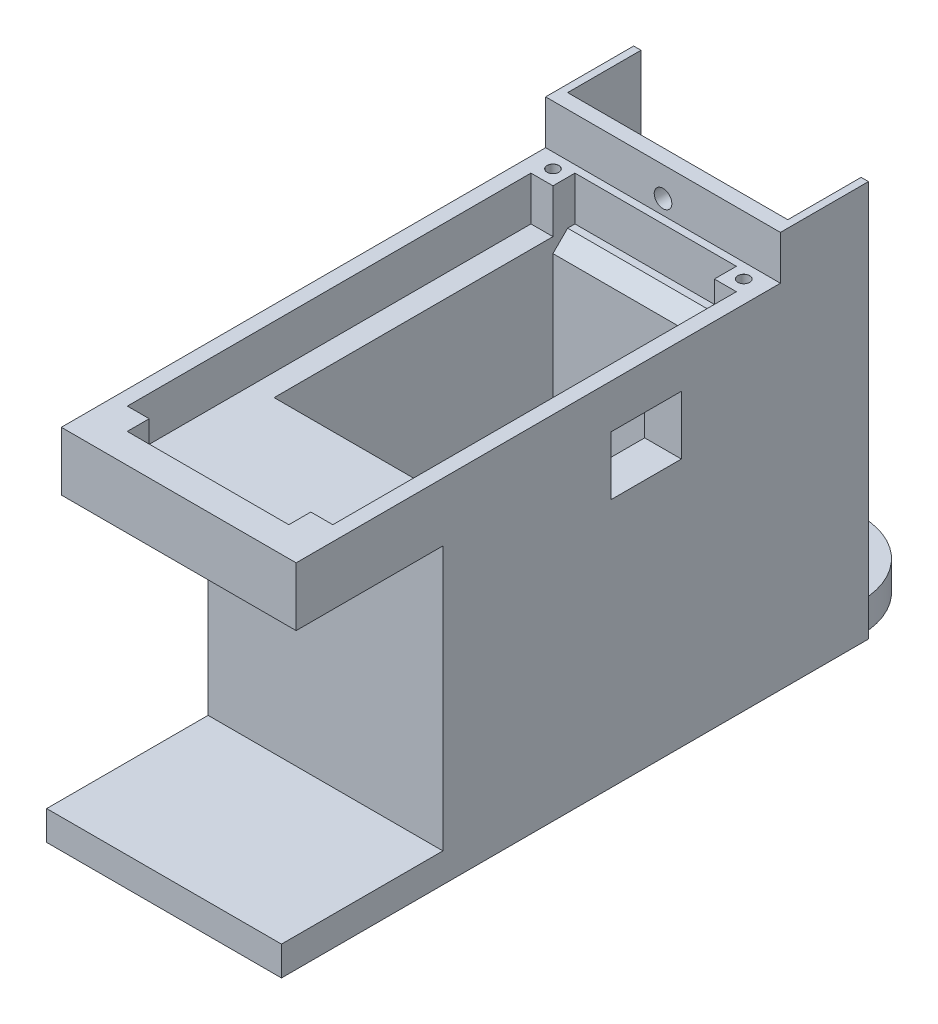
SolidWorks part; units mm, degrees
ref_plane "Front Plane" through (0, 0, 0) normal (0, 0, 1) x (1, 0, 0)
ref_plane "Top Plane" through (0, 0, 0) normal (0, 1, 0) x (1, 0, 0)
ref_plane "Right Plane" through (0, 0, 0) normal (1, 0, 0) x (0, 0, -1)
sketch "Sketch2" plane through (0, 0, 0) normal (0, 1, 0) x (1, 0, 0)
  line L0 (155, 400) -> (160, 400)
  line L1 (0, 0) -> (160, 0)
  line L2 (0, 0) -> (0, 400)
  line L3 (0, 400) -> (5, 400)
  line L4 (160, 0) -> (160, 400)
  line L6 (5, 400) -> (5, 450)
  line L7 (5, 450) -> (155, 450)
  line L8 (155, 400) -> (155, 450)
  dimension "D1" = 160
  dimension "D2" = 400
  dimension "D3" = 5
  dimension "D4" = 5
  dimension "D5" = 50
extrude "Boss-Extrude1" add sketch "Sketch2" along normal blind 20
fillet "Fillet1" radius 50 2 edges at (155, 10, -450) (5, 10, -450)
sketch "Sketch3" plane through (0, 20, 0) normal (0, 1, 0) x (1, 0, 0)
  line L0 (0, 400) -> (0, 340)
  line L1 (0, 400) -> (0, 0) construction
  line L2 (0, 340) -> (160, 340)
  line L3 (160, 0) -> (160, 400) construction
  line L4 (160, 340) -> (160, 400)
  line L5 (160, 400) -> (155, 400)
  line L6 (5, 400) -> (0, 400) construction
  line L7 (155, 400) -> (155, 350)
  line L8 (155, 350) -> (5, 350)
  line L9 (5, 350) -> (5, 400)
  line L10 (5, 400) -> (0, 400)
  dimension "D1" = 5
  dimension "D2" = 5
  dimension "D3" = 50
  dimension "D4" = 10
  dimension "D5" = 150
extrude "Boss-Extrude2" add sketch "Sketch3" along normal blind 250
sketch "Sketch4" plane through (0, 0, -340) normal (0, 0, 1) x (1, 0, 0)
  line L0 (0, 270) -> (160, 270) construction
  line L1 (0, 270) -> (0, 20) construction
  circle A0 centre (80, 250) radius 6
  dimension "D1" = 12
  dimension "D2" = 20
  dimension "D3" = 80
extrude "Cut-Extrude1" cut sketch "Sketch4" against normal blind 10
sketch "Sketch5" plane through (0, 0, -350) normal (0, 0, -1) x (-1, 0, 0)
  circle A0 centre (-80, 250) radius 6
  circle A1 centre (-80, 250) radius 8
  dimension "D1" = 16
  dimension "D2" = 12
extrude "Boss-Extrude3" add sketch "Sketch5" along normal blind 12 contours A1 | A0
fillet "Fillet2" radius 1 2 edges at (74, 250, -362) (72, 250, -362)
sketch "Sketch6" plane through (0, 20, 0) normal (0, 1, 0) x (1, 0, 0)
  line L0 (155, 350) -> (5, 350) construction
  line L1 (30, 350) -> (45, 350)
  line L2 (30, 350) -> (30, 410)
  line L3 (30, 410) -> (45, 410)
  line L4 (45, 350) -> (45, 410)
  line L5 (5, 350) -> (5, 400) construction
  line L6 (115, 350) -> (130, 350)
  line L7 (115, 350) -> (115, 410)
  line L8 (115, 410) -> (130, 410)
  line L9 (130, 350) -> (130, 410)
  line L10 (155, 400) -> (155, 350) construction
  dimension "D1" = 25
  dimension "D2" = 25
  dimension "D3" = 15
  dimension "D4" = 15
  dimension "D5" = 60
extrude "Boss-Extrude4" add sketch "Sketch6" along normal blind 6
sketch "Sketch7" plane through (0, 20, 0) normal (0, 1, 0) x (1, 0, 0)
  line L0 (0, 340) -> (0, 0) construction
  line L1 (55, 220) -> (105, 220)
  line L2 (55, 220) -> (55, 130)
  line L3 (55, 130) -> (105, 130)
  line L4 (105, 220) -> (105, 130)
  line L6 (0, 340) -> (160, 340) construction
  dimension "D1" = 50
  dimension "D2" = 55
  dimension "D3" = 90
  dimension "D4" = 120
extrude "Boss-Extrude5" add sketch "Sketch7" along normal blind 30
sketch "Sketch8" plane through (55, 0, 0) normal (-1, 0, 0) x (0, 0, 1)
  line L0 (-220, 50) -> (-130, 50) construction
  line L1 (-220, 50) -> (-220, 20) construction
  circle A0 centre (-195, 41) radius 3.3
  dimension "D1" = 6.6
  dimension "D2" = 9
  dimension "D3" = 25
extrude "Cut-Extrude2" cut sketch "Sketch8" against normal up to next
sketch "Sketch9" plane through (0, 50, 0) normal (0, 1, 0) x (1, 0, 0)
  line L0 (80, 220) -> (80, 130) construction
  line L1 (71, 186) -> (89, 186)
  line L2 (71, 186) -> (71, 204)
  line L3 (71, 204) -> (89, 204)
  line L4 (89, 186) -> (89, 204)
  line L5 (71, 186) -> (89, 204) construction
  line L6 (71, 204) -> (89, 186) construction
  line L7 (105, 220) -> (55, 220) construction
  line L8 (55, 130) -> (105, 130) construction
  line L9 (55, 175) -> (105, 175) construction
  line L10 (55, 220) -> (55, 130) construction
  line L11 (105, 130) -> (105, 220) construction
  point P0 (80, 195)
  dimension "D1" = 18
  dimension "D2" = 25
extrude "Cut-Extrude3" cut sketch "Sketch9" against normal blind 20
sketch "Sketch10" plane through (0, 50, 0) normal (0, 1, 0) x (1, 0, 0)
  line L0 (55, 130) -> (105, 130)
  line L1 (105, 130) -> (105, 220)
  line L2 (105, 220) -> (55, 220)
  line L3 (55, 220) -> (55, 130)
  line L5 (60, 214) -> (100, 214)
  line L6 (60, 214) -> (60, 159)
  line L8 (100, 214) -> (100, 159)
  arc A0 (60, 159) -> (100, 159) centre (80, 159) ccw
  dimension "D1" = 5
  dimension "D2" = 5
  dimension "D4" = 6
extrude "Boss-Extrude6" add sketch "Sketch10" along normal blind 20
chamfer "Chamfer1" distance 10 distance2 13 1 edges at (60, 60, -214) first distance on face at (60, 60, -186.5)
chamfer "Chamfer2" distance 13 distance2 10 1 edges at (100, 60, -214) first distance on face at (86.5, 60, -214)
fillet "Fillet3" radius 2 4 edges at (100, 60, -204) (87, 60, -214) (73, 60, -214) (60, 60, -204)
sketch "Sketch11" plane through (0, 20, 0) normal (0, 1, 0) x (1, 0, 0)
  line L0 (0, 340) -> (0, 110)
  line L1 (0, 110) -> (160, 110)
  line L2 (160, 110) -> (160, 340)
  line L3 (160, 340) -> (155, 340)
  line L4 (0, 340) -> (160, 340) construction
  line L5 (155, 340) -> (155, 115)
  line L6 (155, 115) -> (5, 115)
  line L7 (5, 115) -> (5, 340)
  line L8 (5, 340) -> (0, 340)
  line L9 (0, 0) -> (160, 0) construction
  dimension "D1" = 5
  dimension "D2" = 5
  dimension "D3" = 5
  dimension "D4" = 110
extrude "Boss-Extrude7" add sketch "Sketch11" along normal blind 220
sketch "Sketch12" plane through (0, 20, 0) normal (0, 1, 0) x (1, 0, 0)
  line L1 (5, 340) -> (25, 340)
  line L2 (5, 340) -> (5, 320)
  line L3 (5, 320) -> (25, 320)
  line L4 (25, 340) -> (25, 320)
  line L5 (155, 340) -> (135, 340)
  line L6 (155, 340) -> (155, 320)
  line L7 (155, 320) -> (135, 320)
  line L8 (135, 340) -> (135, 320)
  line L9 (5, 115) -> (25, 115)
  line L10 (5, 115) -> (5, 135)
  line L11 (5, 135) -> (25, 135)
  line L12 (25, 115) -> (25, 135)
  line L13 (155, 115) -> (135, 115)
  line L14 (155, 115) -> (155, 135)
  line L15 (155, 135) -> (135, 135)
  line L16 (135, 115) -> (135, 135)
  line L17 (5, 320) -> (10, 320)
  line L18 (5, 320) -> (5, 135)
  line L19 (5, 135) -> (10, 135)
  line L20 (10, 320) -> (10, 135)
  line L21 (25, 115) -> (135, 115)
  line L22 (25, 115) -> (25, 120)
  line L23 (25, 120) -> (135, 120)
  line L24 (135, 115) -> (135, 120)
  line L25 (155, 135) -> (150, 135)
  line L26 (155, 135) -> (155, 320)
  line L27 (155, 320) -> (150, 320)
  line L28 (150, 135) -> (150, 320)
  line L29 (135, 340) -> (25, 340)
  line L30 (135, 340) -> (135, 335)
  line L31 (135, 335) -> (25, 335)
  line L32 (25, 340) -> (25, 335)
  line M12 (155, 115) -> (155, 340)
  line M13 (155, 340) -> (5, 340)
  line M14 (5, 340) -> (5, 115)
  line M15 (5, 115) -> (155, 115)
  dimension "D1" = 20
  dimension "D2" = 20
  dimension "D3" = 20
  dimension "D4" = 20
  dimension "D5" = 20
  dimension "D6" = 20
  dimension "D7" = 20
  dimension "D8" = 20
  dimension "D9" = 5
  dimension "D10" = 5
  dimension "D11" = 5
  dimension "D12" = 5
extrude "Boss-Extrude8" add sketch "Sketch12" along normal blind 220 contours L23 L12 L16 M15 | L12 L11 M15 M14 | L20 L3 L11 M14 | L4 L3 M13 M14 | L31 L8 L4 M13 | L8 L7 M13 M12 | L28 L15 L7 M12 | L16 L15 M15 M12 region at (15, 20, -330) region at (80, 20, -337.5) region at (7.5, 20, -227.5) region at (145, 20, -330) region at (15, 20, -125) region at (152.5, 20, -227.5) region at (80, 20, -117.5) region at (145, 20, -125)
sketch "Sketch14" plane through (0, 240, 0) normal (0, 1, 0) x (1, 0, 0)
  line L2 (80, 340) -> (80, 115) construction
  line L3 (0, 340) -> (160, 340) construction
  line L10 (5, 227.5) -> (155, 227.5) construction
  point P0 (15, 330)
  point P31 (145, 330)
hole_wizard "Ø8.0mm Dowel Hole1" positions "Sketch14" profile "Sketch15" hole size "Ø8.0" standard "ANSI Metric"
sketch "Sketch15" plane through (15, 240, -330) normal (1, 0, 0) x (0, 0, 1)
  line L0 (0, 0) -> (0, 18.4034)
  line L1 (0, 18.4034) -> (4, 16)
  line L2 (4, 16) -> (4, 0.025)
  line L3 (4, 0.025) -> (4.025, 0)
  line L5 (4.025, 0) -> (0, 0)
  line L6 (-4, 0.025) -> (-4.025, 0) construction
  line L10 (0, 18.4034) -> (-4, 16) construction
  line L11 (0, -6.35) -> (0, 107.95) construction
  dimension "Hole Dia." = 8
  dimension "Hole Depth" = 16
  dimension "Near C'Sink Dia." = 8.05
  dimension "Near C'Sink Angle" = 90
  dimension "Drill Angle" = 118
sketch "Sketch16" plane through (0, 20, 0) normal (0, 1, 0) x (1, 0, 0)
  line L0 (25, 335) -> (135, 335)
  line L1 (135, 335) -> (25, 335) construction
  line L2 (135, 335) -> (135, 320)
  line L3 (135, 320) -> (150, 320)
  line L4 (150, 320) -> (150, 135)
  line L5 (150, 135) -> (135, 135)
  line L6 (135, 135) -> (135, 120)
  line L7 (135, 120) -> (25, 120)
  line L8 (25, 120) -> (25, 135)
  line L9 (25, 135) -> (10, 135)
  line L10 (10, 135) -> (10, 320)
  line L11 (10, 320) -> (25, 320) construction
  line L12 (10, 320) -> (10, 135) construction
  line L13 (10, 320) -> (25, 320)
  line L15 (25, 320) -> (25, 335)
  line L16 (25, 320) -> (135, 320)
  line L17 (135, 320) -> (135, 130)
  line L18 (135, 130) -> (25, 130)
  line L19 (25, 130) -> (25, 320)
  line M17 (135, 335) -> (25, 335)
  line M18 (25, 335) -> (25, 320)
  line M19 (25, 320) -> (10, 320)
  line M20 (10, 320) -> (10, 135)
  line M21 (10, 135) -> (25, 135)
  line M23 (25, 120) -> (135, 120)
  line M24 (135, 120) -> (135, 135)
  line M25 (135, 135) -> (150, 135)
  line M26 (150, 135) -> (150, 320)
  line M27 (150, 320) -> (135, 320)
  line M28 (135, 320) -> (135, 335)
  line M32 (105, 130) -> (55, 130)
  dimension "D1" = 15
  dimension "D2" = 15
  dimension "D3" = 10
extrude "Boss-Extrude9" add sketch "Sketch16" along normal blind 190 contours L19 M21 M19 M20 | L16 M18 M28 M17 | L17 M27 M25 M26 | L18 L8 M24 M32 M23 region at (80, 20, -327.5) region at (17.5, 20, -227.5) region at (142.5, 20, -227.5) region at (80, 20, -125)
chamfer "Chamfer3" distance 10 angle 45 1 edges at (80, 210, -320)
sketch "Sketch17" plane through (160, 0, 0) normal (1, 0, 0) x (0, 0, -1)
  line L0 (110, 240) -> (340, 240) construction
  line L1 (272.5, 210) -> (224.5, 210)
  line L2 (272.5, 210) -> (272.5, 170)
  line L3 (272.5, 170) -> (224.5, 170)
  line L4 (224.5, 210) -> (224.5, 170)
  line L5 (340, 270) -> (340, 240) construction
  dimension "D1" = 48
  dimension "D2" = 40
  dimension "D3" = 30
  dimension "D4" = 67.5
extrude "Cut-Extrude6" cut sketch "Sketch17" against normal up to next contours L2 L1 L4 L3
sketch "Sketch18" plane through (0, 0, -110) normal (0, 0, 1) x (1, 0, 0)
  line L0 (160, 240) -> (160, 20) construction
  line L1 (0, 240) -> (160, 240)
  line L2 (0, 240) -> (0, 200)
  line L3 (0, 200) -> (160, 200)
  line L4 (160, 240) -> (160, 200)
  line L5 (135, 210) -> (150, 210) construction
  line L6 (10, 210) -> (25, 210) construction
  line L7 (25, 210) -> (135, 210) construction
  line L8 (135, 210) -> (150, 210)
  line L9 (10, 210) -> (25, 210)
  line L10 (25, 210) -> (135, 210)
  line M7 (160, 20) -> (160, 240)
  line M8 (160, 240) -> (0, 240)
  line M9 (0, 240) -> (0, 20)
  dimension "D1" = 10
extrude "Boss-Extrude10" add sketch "Sketch18" along normal blind 100 contours L3 M9 M7 M8 region at (80, 220, -110)
sketch "Sketch19" plane through (0, 0, -120) normal (0, 0, -1) x (-1, 0, 0)
  line L1 (-135, 240) -> (-24.8957, 240)
  line L2 (-135, 240) -> (-135, 210)
  line L3 (-135, 210) -> (-24.8957, 210)
  line L4 (-24.8957, 240) -> (-24.8957, 210)
  line L5 (-25, 210) -> (-135, 210) construction
extrude "Cut-Extrude7" cut sketch "Sketch19" against normal blind 90
sketch "Sketch20" plane through (0, 210, 0) normal (0, 1, 0) x (1, 0, 0)
  line L0 (0, 0) -> (160, 0) construction
  line L1 (0, 0) -> (160, 0)
  circle A0 centre (77.9809, 55) radius 3
  dimension "D2" = 6
  dimension "D1" = 55
extrude "Cut-Extrude8" cut sketch "Sketch20" against normal up to next contours A0 region at (77.9809, 210, -55)
sketch "Sketch21" plane through (0, 0, -135) normal (0, 0, -1) x (-1, 0, 0)
  line L1 (-150, 210) -> (-10, 210)
  line L2 (-150, 210) -> (-150, 240)
  line L3 (-150, 240) -> (-10, 240)
  line L4 (-10, 210) -> (-10, 240)
extrude "Cut-Extrude9" cut sketch "Sketch21" against normal blind 90
